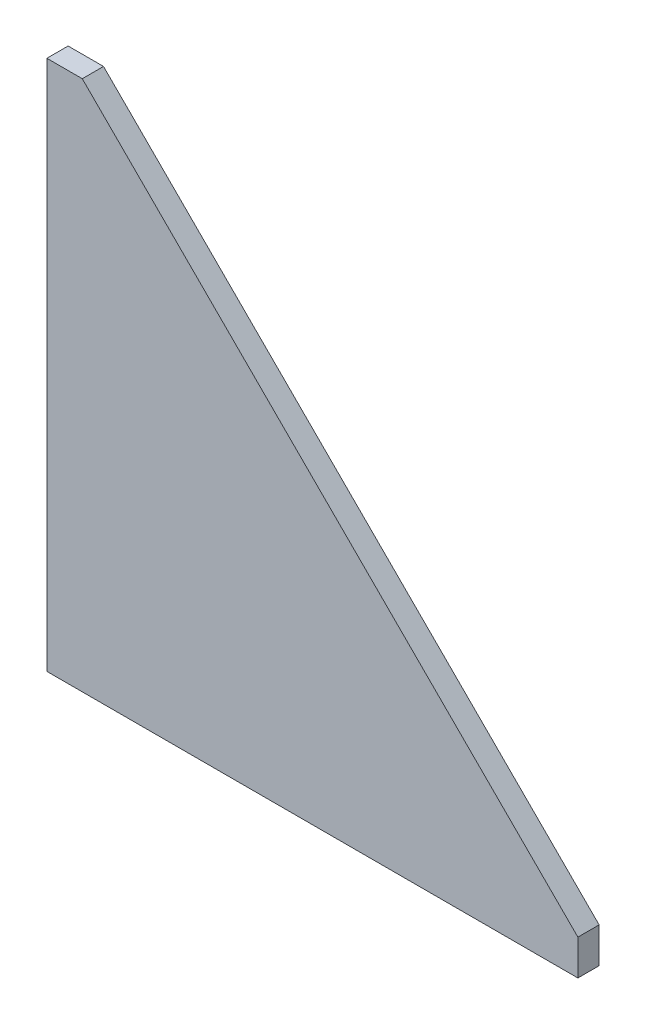
SolidWorks part; units mm, degrees
material "AISI 1020"
ref_plane "Спереди" through (0, 0, 0) normal (0, 0, 1) x (1, 0, 0)
ref_plane "Сверху" through (0, 0, 0) normal (0, 1, 0) x (1, 0, 0)
ref_plane "Справа" through (0, 0, 0) normal (1, 0, 0) x (0, 0, -1)
sketch "Эскиз1" plane through (0, 0, 0) normal (0, 0, 1) x (1, 0, 0)
  line L0 (0, 0) -> (150, 0)
  line L1 (150, 0) -> (150, 10)
  line L2 (150, 10) -> (10, 150)
  line L3 (10, 150) -> (0, 150)
  line L4 (0, 150) -> (0, 0)
  dimension "D1" = 10
  dimension "D2" = 150
base flange "Базовая кромка1" sketch "Эскиз1" thickness 6 reverse thickness direction no parameters "D1"=0.75
sketch "Сгиб-Линии1" plane through (0, 0, 0) normal (0, 1, 0) x (1, 0, 0)
sketch "Граничная рамка1" plane through (0, 0, 0) normal (0, 1, 0) x (1, 0, 0)
sheet metal parameters "Листовой металл3" thickness 6 parameters "D1"=0.75
flat pattern "Развертка3" [suppressed]
sketch "Сгиб-Линии2" plane through (0, 0, 0) normal (0, 1, 0) x (1, 0, 0)
sketch "Граничная рамка2" [suppressed] plane through (0, 0, 0) normal (0, 1, 0) x (1, 0, 0)
